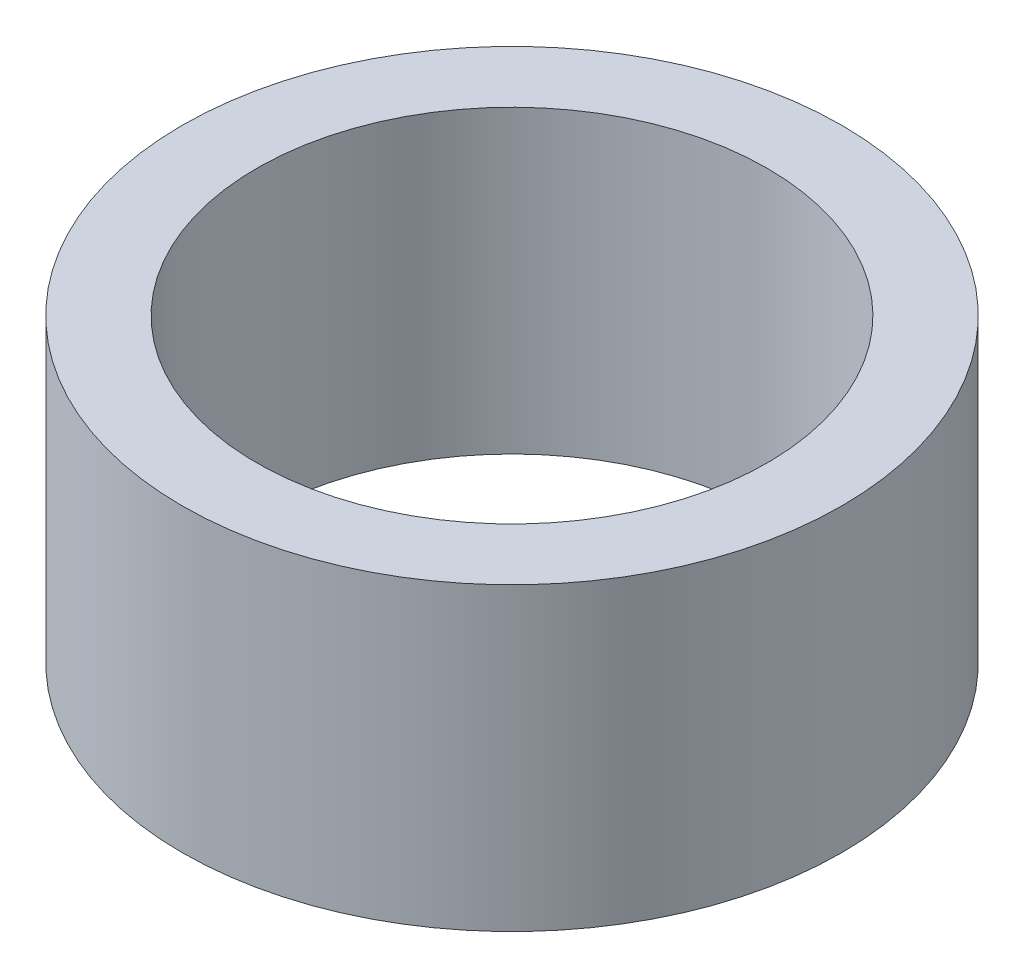
SolidWorks part; units mm, degrees
ref_plane "Front Plane" through (0, 0, 0) normal (0, 0, 1) x (1, 0, 0)
ref_plane "Top Plane" through (0, 0, 0) normal (0, 1, 0) x (1, 0, 0)
ref_plane "Right Plane" through (0, 0, 0) normal (1, 0, 0) x (0, 0, -1)
sketch "Sketch1" plane through (0, 0, 0) normal (0, 1, 0) x (1, 0, 0)
  circle A0 centre (0, 0) radius 15
  dimension "SLEEVE_OD" = 30
extrude "Boss-Extrude1" add sketch "Sketch1" along normal blind 13.6639
sketch "Sketch2" plane through (0, 0, 0) normal (0, 1, 0) x (1, 0, 0)
  circle A0 centre (0, 0) radius 11.6114
  dimension "BORE_D" = 23.2228
extrude "Cut-Extrude1" cut sketch "Sketch2" along normal through all
chamfer "Chamfer1" distance 2.7927 angle 60 rebuild error yes
